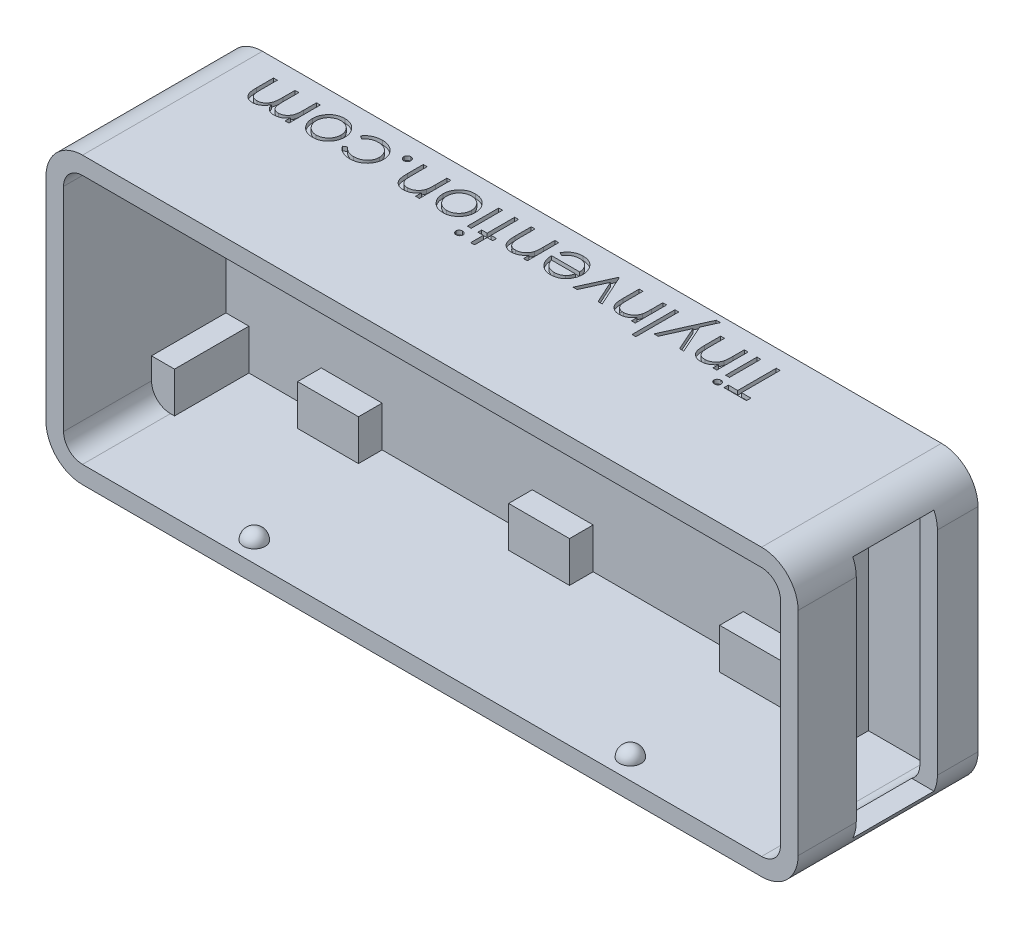
SolidWorks part; units mm, degrees
material "PLA"
ref_plane "Front Plane" through (0, 0, 0) normal (0, 0, 1) x (1, 0, 0)
ref_plane "Top Plane" through (0, 0, 0) normal (0, 1, 0) x (1, 0, 0)
ref_plane "Right Plane" through (0, 0, 0) normal (1, 0, 0) x (0, 0, -1)
sketch "Sketch2" plane through (0, 0, 0) normal (0, 0, 1) x (1, 0, 0)
  line L1 (2.4, -43.153) -> (-47.8, -43.153)
  line L2 (3.8, -44.553) -> (3.8, -60.253)
  line L3 (2.4, -61.653) -> (-47.8, -61.653)
  line L4 (-49.2, -44.553) -> (-49.2, -60.253)
  arc A0 (3.8, -44.553) -> (2.4, -43.153) centre (2.4, -44.553) ccw
  arc A1 (2.4, -61.653) -> (3.8, -60.253) centre (2.4, -60.253) ccw
  arc A2 (-49.2, -60.253) -> (-47.8, -61.653) centre (-47.8, -60.253) ccw
  arc A3 (-49.2, -44.553) -> (-47.8, -43.153) centre (-47.8, -44.553) cw
  point P2 (3.8, -43.153)
  point P9 (-49.2, -61.653)
  point P14 (-49.2, -43.153)
  dimension "D1" = 18.5
  dimension "D3" = 1.4
  dimension "D2" = 53
extrude "Boss-Extrude1" add sketch "Sketch2" along normal blind 12 contours L2 A1 L3 A2 L4 A3 L1 A0
shell "Shell1" thickness 1.3 removed face at (-22.7, -52.403, 12) outward yes
sketch "Sketch3" plane through (0, -61.653, 0) normal (0, 1, 0) x (1, 0, 0)
  line L0 (-9.6, -10.5) -> (-8, -10.5)
  line L1 (2.4, -12) -> (-47.8, -12) construction
  line L2 (5.1, -12) -> (5.1, 1.3) construction
  arc A0 (-8, -10.5) -> (-9.6, -10.5) centre (-8.8, -10.5) ccw
  dimension "D4" = 0.8
  dimension "D1" = 1.5
  dimension "D2" = 13.9
  dimension "D3" = 1.6
revolve "Revolve1" add sketch "Sketch3" angle 360 about L0
ref_plane "Plane1" through (0, -52.403, 0) normal (0, 1, 0) x (1, 0, 0)
mirror "Mirror1" about plane through (0, -52.403, 0) normal (0, 1, 0) of "Revolve1"
sketch "Sketch9" plane through (0, 0, 0) normal (0, 0, 1) x (1, 0, 0)
  line L0 (-47.5, -61.653) -> (-47.5, -58.653)
  line L1 (2.4, -61.653) -> (-47.8, -61.653) construction
  line L2 (2.4, -43.153) -> (-47.8, -43.153) construction
  line L3 (-49.2, -44.553) -> (-49.2, -60.253) construction
  line L4 (-47.5, -58.653) -> (-49.2, -58.653)
  line L8 (2.4, -43.153) -> (-47.8, -43.153)
  line L9 (-49.2, -44.553) -> (-49.2, -60.253)
  line L10 (-47.8, -61.653) -> (2.4, -61.653)
  line L11 (3.8, -60.253) -> (3.8, -44.553)
  line L12 (-47.2, -43.153) -> (-47.8, -43.153)
  line L13 (-49.2, -44.553) -> (-49.2, -60.253)
  line L14 (-47.8, -61.653) -> (-47.5, -61.653)
  arc A4 (3.8, -44.553) -> (2.4, -43.153) centre (2.4, -44.553) ccw
  arc A5 (-47.8, -43.153) -> (-49.2, -44.553) centre (-47.8, -44.553) ccw
  arc A6 (-49.2, -60.253) -> (-47.8, -61.653) centre (-47.8, -60.253) ccw
  arc A7 (2.4, -61.653) -> (3.8, -60.253) centre (2.4, -60.253) ccw
  arc A9 (-47.8, -43.153) -> (-49.2, -44.553) centre (-47.8, -44.553) ccw
  arc A10 (-49.2, -60.253) -> (-47.8, -61.653) centre (-47.8, -60.253) ccw
  line M4 (-49.2, -44.553) -> (-49.2, -60.253)
  arc M5 (-49.2, -60.253) -> (-47.8, -61.653) centre (-47.8, -60.253) ccw
  line M6 (-47.8, -61.653) -> (2.4, -61.653)
  dimension "D1" = 1.7
  dimension "D3" = 3
  dimension "D2" = 0
extrude "Boss-Extrude3" add sketch "Sketch9" along normal blind 5.5 contours L0 L4 M4 M5 M6 region at (-48.3017, -60.0463, 0)
mirror "Mirror2" about plane through (0, -52.403, 0) normal (0, 1, 0) of "Boss-Extrude3"
sketch "Sketch10" plane through (5.1, 0, 0) normal (1, 0, 0) x (0, 0, -1)
  line L0 (6.6, -52.403) -> (-6.6, -52.403) construction
  line L1 (-1.7, -61.403) -> (-7.7, -61.403)
  line L2 (-1.7, -61.403) -> (-1.7, -43.403)
  line L3 (-1.7, -43.403) -> (-7.7, -43.403)
  line L4 (-7.7, -61.403) -> (-7.7, -43.403)
  line L5 (-1.7, -61.403) -> (-7.7, -43.403) construction
  line L6 (-1.7, -43.403) -> (-7.7, -61.403) construction
  line L7 (1.3, -44.553) -> (1.3, -60.253) construction
  point P0 (-4.7, -52.403)
  dimension "D1" = 0
  dimension "D2" = 3
  dimension "D3" = 18
  dimension "D4" = 6
extrude "Cut-Extrude1" cut sketch "Sketch10" against normal blind 2.7
sketch "Sketch11" plane through (0, 0, 0) normal (0, 0, 1) x (1, 0, 0)
  line L0 (6.6, -52.403) -> (-6.6, -52.403) construction
  line L1 (-1.7, -61.653) -> (-3.7, -61.653)
  line L2 (-1.7, -61.653) -> (-1.7, -43.153)
  line L3 (-1.7, -43.153) -> (-3.7, -43.153)
  line L4 (-3.7, -61.653) -> (-3.7, -43.153)
  line L5 (-1.7, -61.653) -> (-3.7, -43.153) construction
  line L6 (-1.7, -43.153) -> (-3.7, -61.653) construction
  line L8 (-50.5, -44.553) -> (-50.5, -60.253) construction
  point P0 (-2.7, -52.403)
  dimension "D1" = 0
  dimension "D2" = 47.8
  dimension "D3" = 2
  dimension "D4" = 18.5
extrude "Boss-Extrude4" add sketch "Sketch11" along normal blind 3.35
ref_plane "Plane2" through (-22.7, 0, 0) normal (-1, 0, 0) x (0, 0, 1)
mirror "Mirror3" about plane through (-22.7, 0, 0) normal (-1, 0, 0) of "Revolve1", "Mirror1"
sketch "Sketch12" plane through (0, 0, 0) normal (0, 0, 1) x (1, 0, 0)
  line L0 (-3.7, -61.653) -> (-47.5, -61.653) construction
  line L1 (-6.45, -61.653) -> (-10.95, -61.653)
  line L2 (-6.45, -61.653) -> (-6.45, -58.653)
  line L3 (-6.45, -58.653) -> (-10.95, -58.653)
  line L4 (-10.95, -61.653) -> (-10.95, -58.653)
  line L5 (-3.7, -43.153) -> (-3.7, -61.653) construction
  dimension "D1" = 3
  dimension "D2" = 4.5
  dimension "D3" = 2.75
extrude "Boss-Extrude5" add sketch "Sketch12" along normal blind 1.75
pattern_linear "LPattern1" count 3 spacing 15.6 along (-1, 0, 0) count 2 spacing 15.5 along (0, 1, 0) of "Boss-Extrude5"
sketch "Sketch19" plane through (0, -41.853, 0) normal (0, 1, 0) x (1, 0, 0)
  line L0 (-7.4973, 0) -> (-45.0839, 0) construction
  text T0 "TinyInvention.com"
extrude "Cut-Extrude4" cut sketch "Sketch19" against normal blind 0.3
sketch "Sketch21" plane through (0, -62.953, 0) normal (0, -1, 0) x (1, 0, 0)
  line L0 (-45.043, 0) -> (0, 0) construction
  text T0 "MinimOSD V1.1 Enclosure" font "Century Gothic" height in points 10
extrude "Cut-Extrude5" cut sketch "Sketch21" against normal blind 0.3
sketch "Sketch22" plane through (0, 0, -1.3) normal (0, 0, -1) x (-1, 0, 0)
  line L1 (3.7, -43.153) -> (3.7, -61.653) construction
  circle A0 centre (11.7, -51.9812) radius 1.75
  dimension "D2" = 3.5
  dimension "D1" = 8
extrude "Cut-Extrude6" [suppressed] cut sketch "Sketch22" against normal blind 1.3
pattern_linear "LPattern2" [suppressed] count 4 spacing 10 of bodies 114
sketch "Sketch23" plane through (-50.5, 0, 0) normal (-1, 0, 0) x (0, 0, 1)
  line L0 (12, -44.553) -> (12, -60.253) construction
  line L2 (12, -61.653) -> (5.5, -61.653) construction
  circle A0 centre (5.5, -52.403) radius 1.75
  dimension "D3" = 3.5
  dimension "D1" = 6.5
  dimension "D2" = 9.25
extrude "Cut-Extrude7" [suppressed] cut sketch "Sketch23" against normal blind 1.3
sketch "Sketch24" plane through (0, -41.853, 0) normal (0, 1, 0) x (1, 0, 0)
  line L0 (2.4, -12) -> (2.4, 1.3) construction
  line L1 (2.4, -12) -> (-47.8, -12) construction
  circle A0 centre (-7.6, -6) radius 1.25
  dimension "D1" = 2.5
  dimension "D2" = 10
  dimension "D3" = 6
extrude "Cut-Extrude8" [suppressed] cut sketch "Sketch24" against normal blind 1.3
pattern_linear "LPattern3" [suppressed] count 4 spacing 10 count 2 spacing 19.8 of bodies 117
equation "\"D1@Boss-Extrude1\" = \"BoxDepth\"'depth"
equation "\"D1@Shell1\"=\"WallThickness\""
equation "\"BoxWidth\"= 18.5mm'inner width"
equation "\"D1@Sketch2\"=\"BoxWidth\""
equation "\"BoxLength\"= 53mm'inner length"
equation "\"D2@Sketch2\"=\"BoxLength\""
equation "\"D3@Sketch2\" = \"CornerRadius\"'inner corner radius"
equation "\"CornerRadius\"= 1.4mm'inner corner radius"
equation "\"BoxDepth\"= 12mm'inner depth"
equation "\"WallThickness\"= 1.3mm"
equation "\"LatchOffEdge\"= 1.5mm"
equation "\"LatchRadius\"= 0.8mm"
equation "\"D2@Sketch3\"=(\"BoxLength\"+\"WallThickness\"*2)/4"
equation "\"D1@Sketch3\"=\"LatchOffEdge\""
equation "\"D3@Sketch3\"=\"LatchRadius\"*2"
equation "\"D4@Sketch3\"=\"LatchRadius\""
equation "\"PortWidth\"= 18mm"
equation "\"PortHeight\"= 6mm"
equation "\"PortOffsetBottom\"= 3mm"
equation "\"D3@Sketch10\"=\"PortWidth\""
equation "\"D2@Sketch10\"=\"PortOffsetBottom\""
equation "\"D4@Sketch10\"=\"PortHeight\""
equation "\"D1@Cut-Extrude1\"=\"WallThickness\"+\"CornerRadius\""
equation "\"D4@Sketch11\"=\"BoxWidth\""
equation "\"D4@LPattern1\"=\"BoxWidth\"-\"D1@Sketch12\""
equation "\"D1@Cut-Extrude6\"=\"WallThickness\""
equation "\"D2@Sketch23\"=\"BoxWidth\"/2"
equation "\"D1@Cut-Extrude7\"=\"WallThickness\""
equation "\"D1@Cut-Extrude8\"=\"WallThickness\""
equation "\"D4@LPattern3\"=\"BoxWidth\"+\"WallThickness\""
